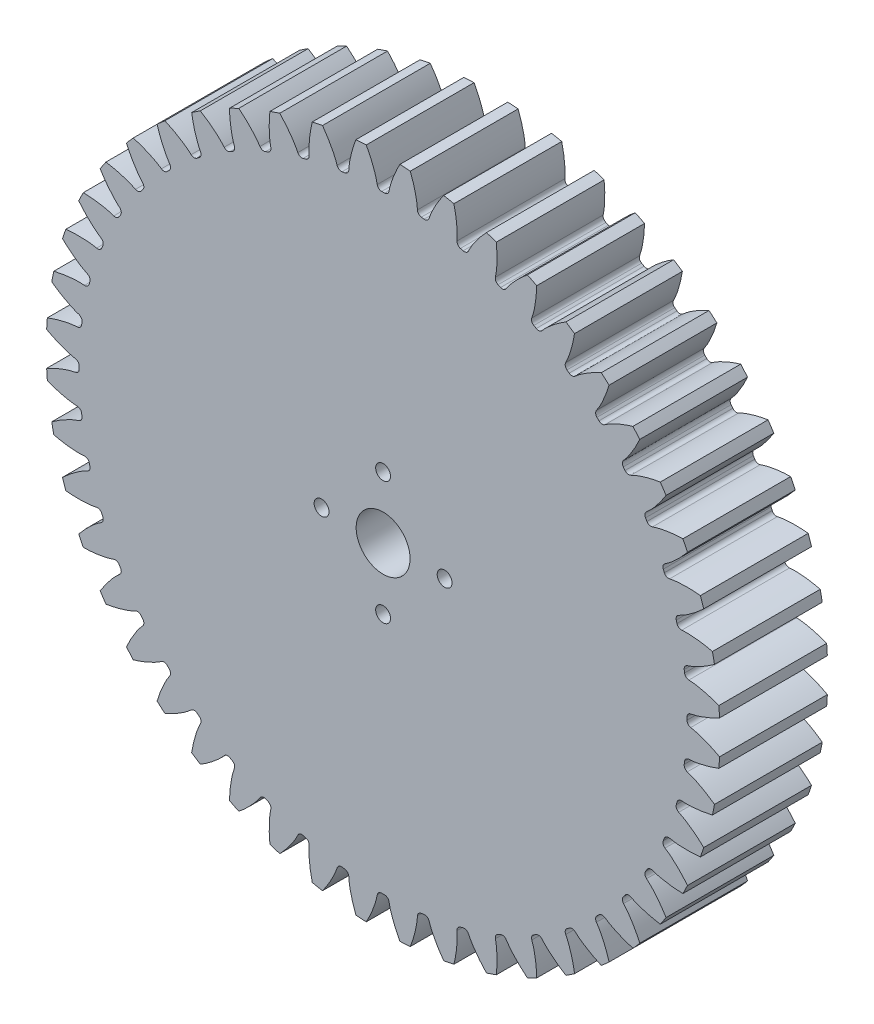
SolidWorks part; units mm, degrees
ref_plane "Front Plane" through (0, 0, 0) normal (0, 0, 1) x (1, 0, 0)
ref_plane "Top Plane" through (0, 0, 0) normal (0, 1, 0) x (1, 0, 0)
ref_plane "Right Plane" through (0, 0, 0) normal (1, 0, 0) x (0, 0, -1)
sketch "Sketch1" plane through (0, 0, 0) normal (0, 0, 1) x (1, 0, 0)
  line L0 (0, 0) -> (0, 38.1) construction
  line L1 (-12.2451, 42.5569) -> (12.2451, 33.6431) construction
  circle A0 centre (0, 0) radius 36.1156 construction
  circle A1 centre (0, 0) radius 39.6875 construction
  circle A2 centre (0, 0) radius 38.1 construction
  circle A3 centre (0, 0) radius 35.8023 construction
  circle A4 centre (0, 0) radius 3.175 construction
  circle A5 centre (0, 0) radius 6.35 construction
  point P8 (203.2, 0)
  point P13 (609.6, 0)
  dimension "OD | Outside Diameter" = 79.375
  dimension "Root Diameter" = 72.2313
  dimension "Gear Pitch Diameter" = 76.2
  dimension "Base Diameter" = 71.6046
  dimension "For Shaft Diameter" = 6.35
  dimension "Hub Diameter" = 12.7
  dimension "Pressure Angle" = 20
  dimension "Number of Teeth" = 1219.2
  dimension "Gear Pitch | Diametral Pitch" = 406.4
sketch "Sketch2" plane through (0, 0, 0) normal (1, 0, 0) x (0, 0, -1)
  line L0 (-6.35, 0) -> (6.35, 0) construction
  line L1 (-6.35, 39.6875) -> (6.35, 39.6875) construction
  point P2 (0, 39.6875)
  point P4 (-5.715, 0)
  point P6 (-5.715, 39.6875)
  dimension "Overall Width" = 12.7
  dimension "Face Width" = 12.065
sketch "Sketch3" plane through (0, 0, 0) normal (0, 0, 1) x (1, 0, 0)
  circle A0 centre (0, 0) radius 39.6875
  circle A1 centre (0, 0) radius 39.6875 construction
extrude "Boss-Extrude1" add sketch "Sketch3" against normal up to vertex (6.35 mm away) and the other way up to vertex (6.35 mm away) up to point (0, 0, -6.35) other way up to point (0, 0, 6.35)
sketch "Sketch4" plane through (0, 0, 0) normal (0, 0, 1) x (1, 0, 0)
  line L0 (0, 0) -> (35.7965, 0.638) construction
  line L2 (0, 0) -> (35.7965, -0.638) construction
  line L4 (35.7965, 0.638) -> (35.7966, 0.638)
  line L5 (35.7966, -0.638) -> (35.7965, -0.638)
  arc A0 (35.7965, 0.638) -> (35.7965, -0.638) centre (0, 0) cw
  arc A3 (39.6379, 1.9832) -> (39.6379, -1.9832) centre (0, 0) cw
  circle A4 centre (0, 0) radius 39.6875 construction
  spline S0 degree 4 poles (35.7966, 0.638) (35.8027, 0.6382) (35.8196, 0.6388) (35.8517, 0.6408) (35.904, 0.6452) (35.9707, 0.6523) (36.0567, 0.6632) (36.1581, 0.6785) (36.2693, 0.6976) (36.3903, 0.7211) (36.5108, 0.7468) (36.631, 0.7746) (36.7506, 0.8043) (36.8954, 0.8425) (37.0688, 0.8916) (37.2712, 0.9536) (37.5005, 1.0294) (37.7337, 1.1125) (37.9629, 1.1992) (38.1941, 1.2923) (38.4174, 1.3864) (38.649, 1.4898) (38.8625, 1.5882) (39.1012, 1.7047) (39.2937, 1.8006) (39.5471, 1.9338) (39.6965, 2.0146) (39.8712, 2.1113) (39.9487, 2.1555) (39.9964, 2.1827) knots 0 0 0 0 0 0.005377 0.015084 0.028532 0.04661 0.064855 0.092111 0.119476 0.146842 0.174209 0.201575 0.228941 0.256307 0.307035 0.361767 0.4165 0.471232 0.525964 0.580697 0.635429 0.690161 0.744894 0.799626 0.854358 0.909091 0.954545 1 1 1 1 1 construction
  spline S1 degree 4 poles (35.7966, 0.638) (35.8027, 0.6382) (35.8196, 0.6388) (35.8517, 0.6408) (35.904, 0.6452) (35.9707, 0.6523) (36.0567, 0.6632) (36.1581, 0.6785) (36.2693, 0.6976) (36.3903, 0.7211) (36.5108, 0.7468) (36.631, 0.7746) (36.7506, 0.8043) (36.8954, 0.8425) (37.0688, 0.8916) (37.2712, 0.9536) (37.5005, 1.0294) (37.7337, 1.1125) (37.9629, 1.1992) (38.1941, 1.2923) (38.4174, 1.3864) (38.649, 1.4898) (38.8625, 1.5882) (39.1012, 1.7047) (39.2937, 1.8006) (39.4921, 1.905) (39.5886, 1.9565) (39.6379, 1.9832) knots 0 0 0 0 0 0.005377 0.015084 0.028532 0.04661 0.064855 0.092111 0.119476 0.146842 0.174209 0.201575 0.228941 0.256307 0.307035 0.361767 0.4165 0.471232 0.525964 0.580697 0.635429 0.690161 0.744894 0.799626 0.854358 0.909091 0.909091 0.909091 0.909091 0.909091
  spline S2 degree 4 poles (35.7966, -0.638) (35.8027, -0.6382) (35.8196, -0.6388) (35.8517, -0.6408) (35.904, -0.6452) (35.9707, -0.6523) (36.0567, -0.6632) (36.1581, -0.6785) (36.2693, -0.6976) (36.3903, -0.7211) (36.5108, -0.7468) (36.631, -0.7746) (36.7506, -0.8043) (36.8954, -0.8425) (37.0688, -0.8916) (37.2712, -0.9536) (37.5005, -1.0294) (37.7337, -1.1125) (37.9629, -1.1992) (38.1941, -1.2923) (38.4174, -1.3864) (38.649, -1.4898) (38.8625, -1.5882) (39.1012, -1.7047) (39.2937, -1.8006) (39.5471, -1.9338) (39.6965, -2.0146) (39.8712, -2.1113) (39.9487, -2.1555) (39.9964, -2.1827) knots 0 0 0 0 0 0.005377 0.015084 0.028532 0.04661 0.064855 0.092111 0.119476 0.146842 0.174209 0.201575 0.228941 0.256307 0.307035 0.361767 0.4165 0.471232 0.525964 0.580697 0.635429 0.690161 0.744894 0.799626 0.854358 0.909091 0.954545 1 1 1 1 1 construction
  spline S3 degree 4 poles (35.7966, -0.638) (35.8027, -0.6382) (35.8196, -0.6388) (35.8517, -0.6408) (35.904, -0.6452) (35.9707, -0.6523) (36.0567, -0.6632) (36.1581, -0.6785) (36.2693, -0.6976) (36.3903, -0.7211) (36.5108, -0.7468) (36.631, -0.7746) (36.7506, -0.8043) (36.8954, -0.8425) (37.0688, -0.8916) (37.2712, -0.9536) (37.5005, -1.0294) (37.7337, -1.1125) (37.9629, -1.1992) (38.1941, -1.2923) (38.4174, -1.3864) (38.649, -1.4898) (38.8625, -1.5882) (39.1012, -1.7047) (39.2937, -1.8006) (39.4921, -1.905) (39.5886, -1.9565) (39.6379, -1.9832) knots 0 0 0 0 0 0.005377 0.015084 0.028532 0.04661 0.064855 0.092111 0.119476 0.146842 0.174209 0.201575 0.228941 0.256307 0.307035 0.361767 0.4165 0.471232 0.525964 0.580697 0.635429 0.690161 0.744894 0.799626 0.854358 0.909091 0.909091 0.909091 0.909091 0.909091
  dimension "D1" = 71.6043
extrude "Cut-Extrude1" cut sketch "Sketch4" against normal through all both and the other way through all
fillet "Fillet1" radius 0.5326 2 edges at (35.7965, -0.638, 0) (35.7965, 0.638, 0)
pattern_circular "CirPattern1" count 48 over 360 about axis through (0, 0, 6.35) along (0, 0, -1) of "Cut-Extrude1", "Fillet1"
sketch "Sketch6" plane through (0, 0, 0) normal (0, 1, 0) x (1, 0, 0)
  line L0 (0, 10.0524) -> (0, -11.762) construction
sketch "Sketch7" plane through (0, 0, 0) normal (0, 0, 1) x (1, 0, 0)
  circle A0 centre (7.25, 0) radius 0.877
  dimension "D2" = 1.754
  dimension "D1" = 7.25
extrude "Cut-Extrude2" cut sketch "Sketch7" against normal through all both and the other way through all
pattern_circular "CirPattern2" count 4 over 360 about axis through (0, 0, -10.0524) along (0, 0, 1) of "Cut-Extrude2"
sketch "Sketch8" plane through (0, 0, 6.35) normal (0, 0, 1) x (1, 0, 0)
  circle A0 centre (0, 0) radius 3.175
  dimension "D1" = 6.35
extrude "Cut-Extrude3" cut sketch "Sketch8" against normal through all
equation "\"Root Diameter@Sketch1\"=\"Root Diameter\""
equation "\"OD | Outside Diameter@Sketch1\"=\"Outside Diameter\""
equation "\"D1@CirPattern1\"=\"Number of Teeth\""
equation "\"Diametral Pitch\"= 16"
equation "\"Number of Teeth\"= 48"
equation "\"Pressure Angle\"=20"
equation "\"Pitch Diameter\"= \"Number of Teeth\" / \"Diametral Pitch\""
equation "\"Base Diameter\"= \"Pitch Diameter\" * cos ( \"Pressure Angle\" )"
equation "\"Outside Diameter\"= ( \"Number of Teeth\" + 2 ) / \"Diametral Pitch\""
equation "\"Dedendum\"= 1.25 / \"Diametral Pitch\""
equation "\"Root Diameter\"= \"Pitch Diameter\" - ( 2 * \"Dedendum\" )"
equation "\"Pitch Angle\"= 360deg / \"Number of Teeth\""
equation "\"Alpha\"= sqr ( \"Pitch Diameter\" ^ 2 - \"Base Diameter\" ^ 2 ) / \"Base Diameter\" * 180 / PI - \"Pressure Angle\""
equation "\"Beta\"= ( \"Pitch Angle\" / 4 - \"Alpha\" )"
equation "\"Phi\"= sqr ( ( \"Outside Diameter\" / 2 ) ^ 2 - ( \"Base Diameter\" / 2 ) ^ 2 ) / ( \"Base Diameter\" / 2 )"
equation "\"Addendum\"= 1 / \"Diametral Pitch\""
equation "\"WorkingDepth\"= 2 / \"Diametral Pitch\""
equation "\"WholeDepth\"= 2.25 / \"Diametral Pitch\""
equation "\"Clearance\"= 0.25 / \"Diametral Pitch\""
equation "\"ToothThickness\"= ( pi * 2 ) / \"Diametral Pitch\""
equation "\"CircularPitch\"= pi / \"Diametral Pitch\""
equation "\"Number of Teeth@Sketch1\"=\"Number of Teeth\""
equation "\"Gear Pitch | Diametral Pitch@Sketch1\"=\"Diametral Pitch\""
equation "\"Pressure Angle@Sketch1\"=\"Pressure Angle\""
equation "\"Gear Pitch Diameter@Sketch1\"=\"Pitch Diameter\""
equation "\"Base Diameter@Sketch1\"=\"Base Diameter\""
equation "\"Fillet\"= \"Clearance\" * cos ( \"Pressure Angle\" ) * tan ( ( 90 + \"Pressure Angle\" ) / 2 )"
equation "\"D1@Fillet1\"=\"Fillet\""
equation "\"D1@Sketch4\"=if( \"Base Diameter\">\"Root Diameter\",\"Root Diameter\",\"Base Diameter\"-.00001)"
equation "\"D1@Fillet2\"=\"Fillet\""
equation "\"D1@Sketch7\"=7.25mm"
equation "\"D2@Sketch7\" = 1.5mm + \"normTol\""
equation "\"tightTol\"= 0.005in"
equation "\"normTol\"= 0.01in"
equation "\"looseTol\"= 0.02in"
